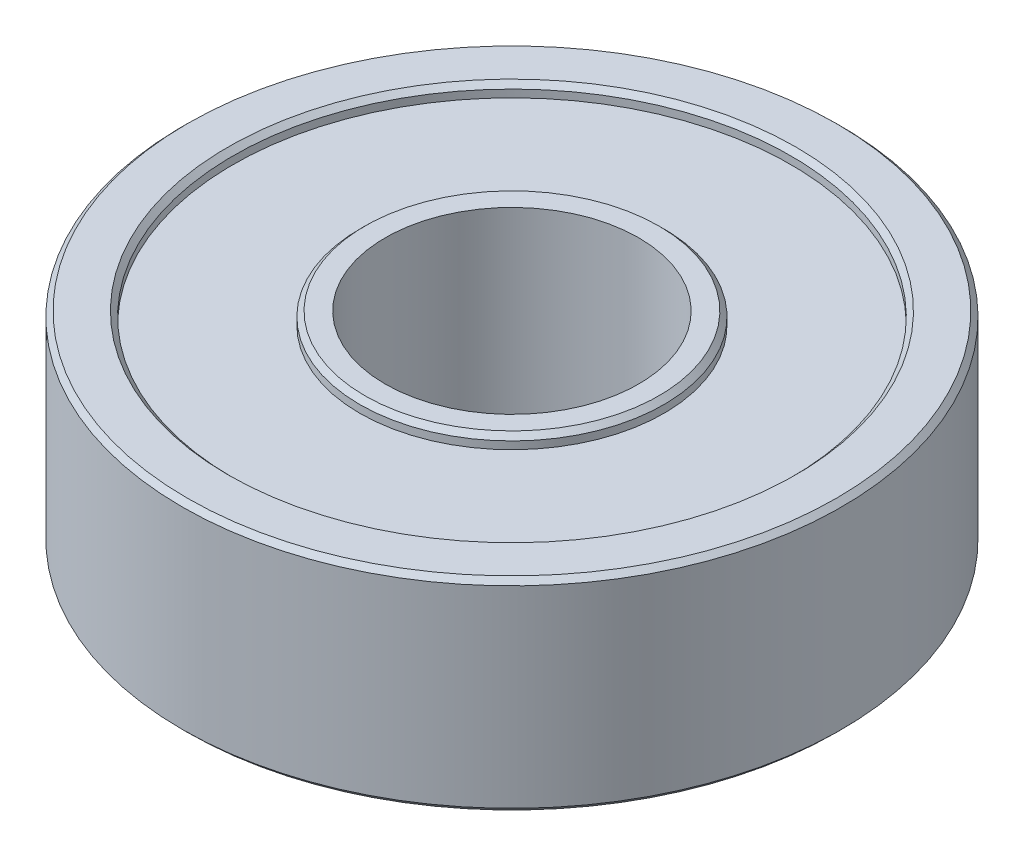
SolidWorks part; units mm, degrees
ref_plane "Front Plane" through (0, 0, 0) normal (0, 0, 1) x (1, 0, 0)
ref_plane "Top Plane" through (0, 0, 0) normal (0, 1, 0) x (1, 0, 0)
ref_plane "Right Plane" through (0, 0, 0) normal (1, 0, 0) x (0, 0, -1)
sketch "Sketch1" plane through (0, 0, 0) normal (0, 1, 0) x (1, 0, 0)
  circle A1 centre (0, 0) radius 13
  circle A2 centre (0, 0) radius 5
extrude "Boss-Extrude1" add sketch "Sketch1" along normal blind 8
sketch "Sketch2" plane through (0, 8, 0) normal (0, 1, 0) x (1, 0, 0)
  circle A0 centre (0, 0) radius 6
  circle A1 centre (0, 0) radius 11
  dimension "D1" = 22
  dimension "D2" = 12
extrude "Cut-Extrude1" cut sketch "Sketch2" against normal blind 0.5
extrude "Cut-Extrude2" cut sketch "Sketch2<2>" along normal blind 0.5 from surface starting at face at (0, 0, 13)
sketch "Sketch2<2>" plane through (0, 8, 0) normal (0, 1, 0) x (1, 0, 0) same geometry as "Sketch2"
chamfer "Chamfer1" distance 0.2 angle 45 6 edges at (0, 8, 11) (0, 0, 6) (0, 8, 6) (0, 0, 11) (0, 0, 13) (0, 8, 13)
